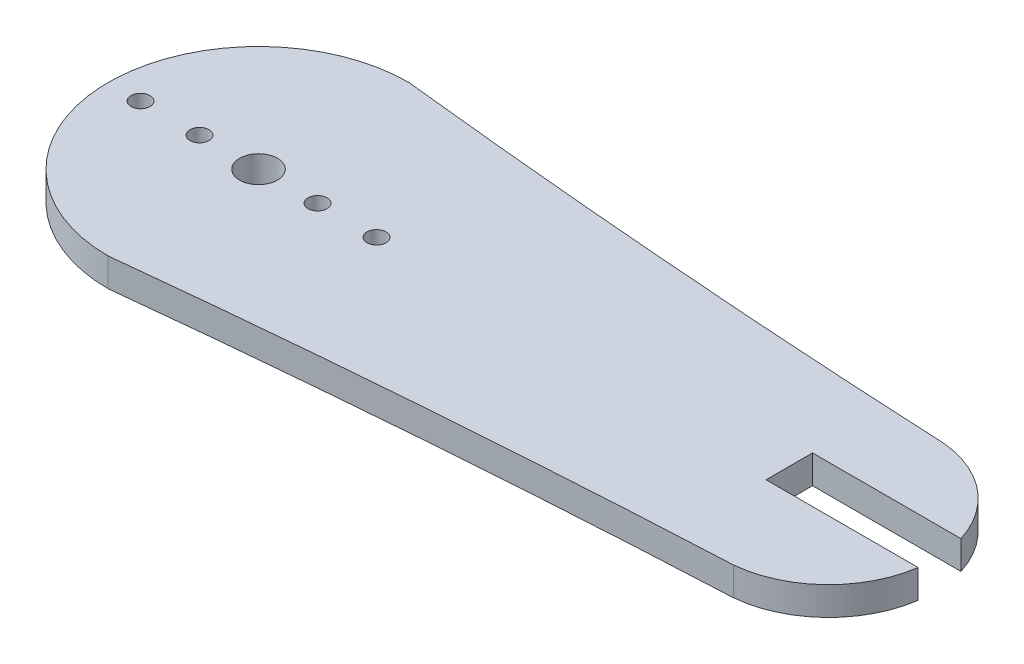
SolidWorks part; units mm, degrees
ref_plane "Front Plane" through (0, 0, 0) normal (0, 0, 1) x (1, 0, 0)
ref_plane "Top Plane" through (0, 0, 0) normal (0, 1, 0) x (1, 0, 0)
ref_plane "Right Plane" through (0, 0, 0) normal (1, 0, 0) x (0, 0, -1)
sketch "Sketch1" plane through (0, 0, 0) normal (0, 1, 0) x (1, 0, 0)
  line L1 (48.1331, -16.4404) -> (48.1331, -11.5404)
  line L3 (48.1331, -11.5404) -> (63.7931, -11.5404)
  line L4 (48.1331, -16.4404) -> (64.1769, -16.4404)
  circle A3 centre (-7.0224, -14.8404) radius 2
  circle A4 centre (-0.7974, -14.8404) radius 1
  circle A5 centre (5.4276, -14.8404) radius 1
  circle A6 centre (-19.4724, -14.8404) radius 1
  circle A7 centre (-13.2474, -14.8404) radius 1
  arc A8 (-3.6693, 0.6611) -> (-3.6693, -30.3419) centre (-7.0224, -14.8404) ccw
  arc A9 (53.1355, -25.9972) -> (64.1769, -16.4404) centre (53.1355, -14.8404) ccw
  arc A12 (-7.0224, 1.0196) -> (54.1898, -3.7336) centre (100.965, 995.1718) ccw
  arc A15 (54.1898, -25.9473) -> (-7.0224, -30.7004) centre (100.965, -1024.8527) ccw
  arc A16 (63.7931, -11.5404) -> (53.1355, -3.6837) centre (53.1355, -14.8404) ccw
  point P11 (48.1331, -23.4993)
  point P16 (-0.7974, -14.8404)
  point P17 (5.4276, -14.8404)
  point P23 (-7.0224, 1.0196)
  point P27 (-19.1224, -14.8404)
  point P28 (-13.5224, -14.8404)
  point P29 (53.1355, -3.6837)
  point P30 (53.1355, -25.9972)
  point P31 (-7.0224, -30.7004)
  dimension "D1" = 6.225
  dimension "D3" = 6.225
  dimension "D4" = 6.225
  dimension "D6" = 2
  dimension "D7" = 2
  dimension "D8" = 4
  dimension "D9" = 4.9
  dimension "D2" = 10
  dimension "D5" = 6.225
extrude "Boss-Extrude1" add sketch "Sketch1" along normal blind 3 contours L4 L1 L3 A7 A3 A4 A5 A6 region at (17.0732, 0, 14.8723)
